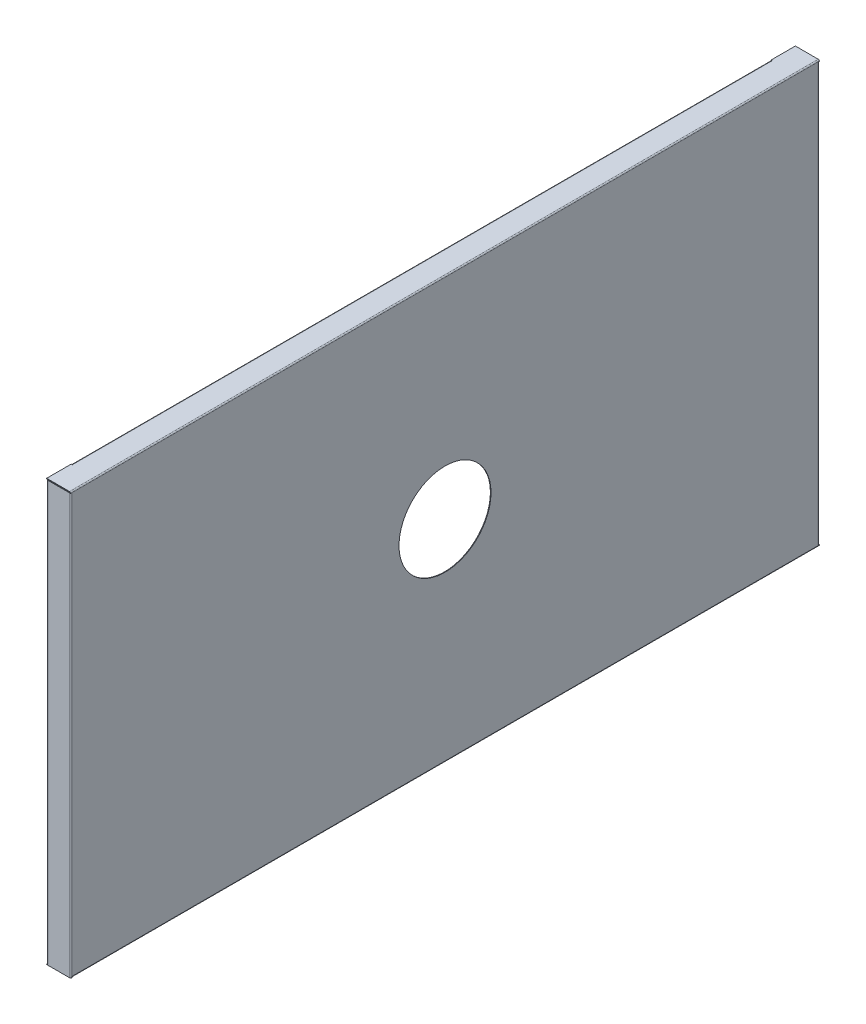
SolidWorks part; units mm, degrees
note: The reader was unsure of these and kept them because the rebuilt part matched: flange length of "Edge-Flange1", "Edge-Flange2", "Edge-Flange3", "Edge-Flange4", "Edge-Flange5", "Edge-Flange6", "Edge-Flange7", "Edge-Flange8".
ref_plane "Front Plane" through (0, 0, 0) normal (0, 0, 1) x (1, 0, 0)
ref_plane "Top Plane" through (0, 0, 0) normal (0, 1, 0) x (1, 0, 0)
ref_plane "Right Plane" through (0, 0, 0) normal (1, 0, 0) x (0, 0, -1)
sketch "Sketch1" plane through (0, 0, 0) normal (1, 0, 0) x (0, 0, -1)
  line L1 (-467.95, -263.2) -> (467.95, -263.2)
  line L2 (-467.95, -263.2) -> (-467.95, 263.2)
  line L3 (-467.95, 263.2) -> (467.95, 263.2)
  line L4 (467.95, -263.2) -> (467.95, 263.2)
  line L5 (-467.95, -263.2) -> (467.95, 263.2) construction
  line L6 (-467.95, 263.2) -> (467.95, -263.2) construction
  circle A0 centre (0, 0) radius 57.5
  point P0 (0, 0)
  dimension "D3" = 115
  dimension "D1" = 935.9
  dimension "D2" = 526.4
base flange "Base-Flange1" sketch "Sketch1" thickness 0.7366 reverse thickness direction no parameters "D1"=0.7366
edge flange "Edge-Flange1" sketch "Sketch8" flange angle 90 flange length 30 flange position material inside bend radius 0.7366 thickness 0.7366 relief rectangular parameters "D6"=10
sketch "Sketch8" plane through (-0.7366, 263.2, 0) normal (0, 1, 0) x (0, 0, -1)
  line L0 (467.95, 0) -> (-467.95, 0) construction
  line L1 (467.95, 0) -> (-467.95, 0)
  line L2 (-467.95, 0) -> (-467.95, 29.2634)
  line L3 (-467.95, 29.2634) -> (467.95, 29.2634)
  line L4 (467.95, 29.2634) -> (467.95, 0)
bend "EdgeBend1" bend radius 0.7366 bend angle 90 parameters "D5"=1
edge flange "Edge-Flange2" sketch "Sketch11" flange angle 90 flange length 30 flange position material inside bend radius 0.7366 thickness 0.7366 relief none parameters "D6"=10
sketch "Sketch11" plane through (-0.7366, 0, 467.95) normal (0, 0, 1) x (0, 1, 0)
  line L0 (261.7268, 0) -> (-263.2, 0) construction
  line L1 (261.7268, 0) -> (-263.2, 0)
  line L2 (-263.2, 0) -> (-263.2, 29.2634)
  line L3 (-263.2, 29.2634) -> (261.7268, 29.2634)
  line L4 (261.7268, 29.2634) -> (261.7268, 0)
bend "EdgeBend2" bend radius 0.7366 bend angle 90 parameters "D5"=2
edge flange "Edge-Flange3" sketch "Sketch14" flange angle 90 flange length 30 flange position material inside bend radius 0.7366 thickness 0.7366 relief none parameters "D6"=10
sketch "Sketch14" plane through (-0.7366, -263.2, 0) normal (0, -1, 0) x (0, 0, 1)
  line L0 (466.4768, 0) -> (-467.95, 0) construction
  line L1 (466.4768, 0) -> (-467.95, 0)
  line L2 (-467.95, 0) -> (-467.95, 29.2634)
  line L3 (-467.95, 29.2634) -> (466.4768, 29.2634)
  line L4 (466.4768, 29.2634) -> (466.4768, 0)
bend "EdgeBend3" bend radius 0.7366 bend angle 90 parameters "D5"=3
edge flange "Edge-Flange4" sketch "Sketch17" flange angle 90 flange length 30 flange position material inside bend radius 0.7366 thickness 0.7366 relief none parameters "D6"=10
sketch "Sketch17" plane through (-0.7366, 0, -467.95) normal (0, 0, -1) x (0, -1, 0)
  line L0 (261.7268, 0) -> (-261.7268, 0) construction
  line L1 (261.7268, 0) -> (-261.7268, 0)
  line L2 (-261.7268, 0) -> (-261.7268, 29.2634)
  line L3 (-261.7268, 29.2634) -> (261.7268, 29.2634)
  line L4 (261.7268, 29.2634) -> (261.7268, 0)
bend "EdgeBend4" bend radius 0.7366 bend angle 90 parameters "D5"=4
edge flange "Edge-Flange5" sketch "Sketch20" flange angle 90 flange length 30 flange position material inside bend radius 0.7366 thickness 0.7366 relief rectangular parameters "D6"=10
sketch "Sketch20" plane through (-30, 262.4634, 0) normal (-1, 0, 0) x (0, 0, -1)
  line L0 (467.95, 0) -> (-467.95, 0) construction
  line L1 (437.0134, 0) -> (-437.0134, 0)
  line L2 (-437.0134, 0) -> (-437.0134, 29.2634)
  line L3 (-437.0134, 29.2634) -> (437.0134, 29.2634)
  line L4 (437.0134, 29.2634) -> (437.0134, 0)
  line L5 (467.2134, 524.1902) -> (467.2134, 0.7366) construction
  line L6 (-467.2134, 0.7366) -> (-467.2134, 525.6634) construction
  dimension "D1" = 30.2
  dimension "D2" = 30.2
bend "EdgeBend5" bend radius 0.7366 bend angle 90 parameters "D5"=5
edge flange "Edge-Flange6" sketch "Sketch23" flange angle 90 flange length 30 flange position material inside bend radius 0.7366 thickness 0.7366 relief rectangular parameters "D6"=10
sketch "Sketch23" plane through (-30, -262.4634, 0) normal (-1, 0, 0) x (0, 0, 1)
  line L0 (466.4768, 0) -> (-467.95, 0) construction
  line L1 (437.0134, 0) -> (-437.0134, 0)
  line L2 (-437.0134, 0) -> (-437.0134, 29.2634)
  line L3 (-437.0134, 29.2634) -> (437.0134, 29.2634)
  line L4 (437.0134, 29.2634) -> (437.0134, 0)
  line L5 (467.2134, 524.1902) -> (467.2134, -0.7366) construction
  line L6 (-467.2134, 0.7366) -> (-467.2134, 524.1902) construction
  dimension "D1" = 30.2
  dimension "D2" = 30.2
bend "EdgeBend6" bend radius 0.7366 bend angle 90 parameters "D5"=6
edge flange "Edge-Flange7" sketch "Sketch26" flange angle 90 flange length 30 flange position material inside bend radius 0.7366 thickness 0.7366 relief rectangular parameters "D6"=10
sketch "Sketch26" plane through (-30, 0, -467.2134) normal (-1, 0, 0) x (0, -1, 0)
  line L0 (261.7268, 0) -> (-261.7268, 0) construction
  line L1 (261.7268, 0) -> (-261.7268, 0)
  line L2 (-261.7268, 0) -> (-261.7268, 29.2634)
  line L3 (-261.7268, 29.2634) -> (261.7268, 29.2634)
  line L4 (261.7268, 29.2634) -> (261.7268, 0)
bend "EdgeBend7" bend radius 0.7366 bend angle 90 parameters "D5"=7
edge flange "Edge-Flange8" sketch "Sketch29" flange angle 90 flange length 30 flange position material inside bend radius 0.7366 thickness 0.7366 relief rectangular parameters "D6"=10
sketch "Sketch29" plane through (-30, 0, 467.2134) normal (1, 0, 0) x (0, -1, 0)
  line L1 (263.2, 0) -> (-261.7268, 0) construction
  line L2 (-261.7268, 0) -> (-261.7268, 29.2634)
  line L3 (-261.7268, 29.2634) -> (262.2634, 29.2634)
  line L4 (262.2634, 29.2634) -> (262.2634, 0)
  line L5 (262.2634, 0) -> (-261.7268, 0)
  line L6 (262.4634, 0.7366) -> (262.4634, 29.8317) construction
  dimension "D1" = 0.2
bend "EdgeBend8" bend radius 0.7366 bend angle 90 parameters "D5"=8
sketch "Bend-Lines1" [suppressed] plane through (0, 0, 0) normal (0, 1, 0) x (1, 0, 0)
sketch "Bounding-Box1" [suppressed] plane through (0, 0, 0) normal (0, 1, 0) x (1, 0, 0)
sheet metal parameters "Sheet-Metal1" thickness 0.7366 parameters "D1"=0.7366
flat pattern "Flat-Pattern1" [suppressed]
sketch "Bend-Lines2" plane through (0, 0, 0) normal (0, 1, 0) x (1, 0, 0)
sketch3d "Bounding-Box2" [suppressed]
  line L0 (-468.45, -263.7, 0) -> (468.45, -263.7, 0) construction
  line L1 (-468.45, 263.7, 0) -> (468.45, 263.7, 0) construction
  line L2 (-468.45, -263.7, 0) -> (-468.45, 263.7, 0) construction
  line L3 (468.45, -263.7, 0) -> (468.45, 263.7, 0) construction
sheet metal parameters "Sheet-Metal2" thickness 0.7366 parameters "D1"=0.7366
flat pattern "Flat-Pattern1"
sketch "Bend-Lines2" plane through (0, 0, 0) normal (1, 0, 0) x (0, 0, -1)
  line L0 (468.45, 263.0946) -> (-468.45, 263.0946) construction
  line L1 (468.45, 263.0946) -> (-468.45, 263.0946) construction
sketch3d "Bounding-Box2" [suppressed]
  line L0 (468.45, -263.7, 0) -> (-468.45, -263.7, 0) construction
  line L1 (468.45, 292.4892, 0) -> (-468.45, 292.4892, 0) construction
  line L2 (468.45, -263.7, 0) -> (468.45, 292.4892, 0) construction
  line L3 (-468.45, -263.7, 0) -> (-468.45, 292.4892, 0) construction
bend of the flat pattern "Flatten-<EdgeBend1>1"
sheet metal parameters "Sheet-Metal3" thickness 0.7366 parameters "D1"=0.7366
flat pattern "Flat-Pattern1"
sketch "Bend-Lines2" plane through (0, 0, 0) normal (1, 0, 0) x (0, 0, -1)
  line L0 (468.45, 263.0946) -> (-468.45, 263.0946) construction
  line L1 (468.45, 263.0946) -> (-468.45, 263.0946) construction
  line L2 (-467.8446, 262.2268) -> (-467.8446, -263.7) construction
  line L3 (-467.8446, 262.2268) -> (-467.8446, -263.7) construction
sketch3d "Bounding-Box2" [suppressed]
  line L0 (468.45, -263.7, 0) -> (-497.2392, -263.7, 0) construction
  line L1 (468.45, 292.4892, 0) -> (-497.2392, 292.4892, 0) construction
  line L2 (468.45, -263.7, 0) -> (468.45, 292.4892, 0) construction
  line L3 (-497.2392, -263.7, 0) -> (-497.2392, 292.4892, 0) construction
bend of the flat pattern "Flatten-<EdgeBend1>1"
bend of the flat pattern "Flatten-<EdgeBend2>1"
sheet metal parameters "Sheet-Metal4" thickness 0.7366 parameters "D1"=0.7366
flat pattern "Flat-Pattern1"
sketch "Bend-Lines2" plane through (0, 0, 0) normal (1, 0, 0) x (0, 0, -1)
  line L0 (468.45, 263.0946) -> (-468.45, 263.0946) construction
  line L1 (468.45, 263.0946) -> (-468.45, 263.0946) construction
  line L2 (-467.8446, 262.2268) -> (-467.8446, -263.7) construction
  line L3 (-467.8446, 262.2268) -> (-467.8446, -263.7) construction
  line L4 (-466.9768, -263.0946) -> (468.45, -263.0946) construction
  line L5 (-466.9768, -263.0946) -> (468.45, -263.0946) construction
sketch3d "Bounding-Box2" [suppressed]
  line L0 (468.45, -292.4892, 0) -> (-497.2392, -292.4892, 0) construction
  line L1 (468.45, 292.4892, 0) -> (-497.2392, 292.4892, 0) construction
  line L2 (468.45, -292.4892, 0) -> (468.45, 292.4892, 0) construction
  line L3 (-497.2392, -292.4892, 0) -> (-497.2392, 292.4892, 0) construction
bend of the flat pattern "Flatten-<EdgeBend1>1"
bend of the flat pattern "Flatten-<EdgeBend2>1"
bend of the flat pattern "Flatten-<EdgeBend3>1"
sheet metal parameters "Sheet-Metal5" thickness 0.7366 parameters "D1"=0.7366
flat pattern "Flat-Pattern1"
sketch "Bend-Lines2" plane through (0, 0, 0) normal (1, 0, 0) x (0, 0, -1)
  line L0 (468.45, 263.0946) -> (-468.45, 263.0946) construction
  line L1 (468.45, 263.0946) -> (-468.45, 263.0946) construction
  line L2 (-467.8446, 262.2268) -> (-467.8446, -263.7) construction
  line L3 (-467.8446, 262.2268) -> (-467.8446, -263.7) construction
  line L4 (-466.9768, -263.0946) -> (468.45, -263.0946) construction
  line L5 (-466.9768, -263.0946) -> (468.45, -263.0946) construction
  line L6 (467.8446, -262.2268) -> (467.8446, 262.2268) construction
  line L7 (467.8446, -262.2268) -> (467.8446, 262.2268) construction
sketch3d "Bounding-Box2" [suppressed]
  line L0 (497.2392, -292.4892, 0) -> (-497.2392, -292.4892, 0) construction
  line L1 (497.2392, 292.4892, 0) -> (-497.2392, 292.4892, 0) construction
  line L2 (497.2392, -292.4892, 0) -> (497.2392, 292.4892, 0) construction
  line L3 (-497.2392, -292.4892, 0) -> (-497.2392, 292.4892, 0) construction
bend of the flat pattern "Flatten-<EdgeBend1>1"
bend of the flat pattern "Flatten-<EdgeBend2>1"
bend of the flat pattern "Flatten-<EdgeBend3>1"
bend of the flat pattern "Flatten-<EdgeBend4>1"
sheet metal parameters "Sheet-Metal6" thickness 0.7366 parameters "D1"=0.7366
flat pattern "Flat-Pattern1"
sketch "Bend-Lines2" plane through (0, 0, 0) normal (1, 0, 0) x (0, 0, -1)
  line L0 (468.45, 263.0946) -> (-468.45, 263.0946) construction
  line L1 (468.45, 263.0946) -> (-468.45, 263.0946) construction
  line L2 (-467.8446, 262.2268) -> (-467.8446, -263.7) construction
  line L3 (-467.8446, 262.2268) -> (-467.8446, -263.7) construction
  line L4 (-466.9768, -263.0946) -> (468.45, -263.0946) construction
  line L5 (-466.9768, -263.0946) -> (468.45, -263.0946) construction
  line L6 (467.8446, -262.2268) -> (467.8446, 262.2268) construction
  line L7 (467.8446, -262.2268) -> (467.8446, 262.2268) construction
  line L8 (437.5134, 291.8838) -> (-437.5134, 291.8838) construction
  line L9 (437.5134, 291.8838) -> (-437.5134, 291.8838) construction
sketch3d "Bounding-Box2" [suppressed]
  line L0 (497.2392, -292.4892, 0) -> (-497.2392, -292.4892, 0) construction
  line L1 (497.2392, 321.2783, 0) -> (-497.2392, 321.2783, 0) construction
  line L2 (497.2392, -292.4892, 0) -> (497.2392, 321.2783, 0) construction
  line L3 (-497.2392, -292.4892, 0) -> (-497.2392, 321.2783, 0) construction
bend of the flat pattern "Flatten-<EdgeBend1>1"
bend of the flat pattern "Flatten-<EdgeBend2>1"
bend of the flat pattern "Flatten-<EdgeBend3>1"
bend of the flat pattern "Flatten-<EdgeBend4>1"
bend of the flat pattern "Flatten-<EdgeBend5>1"
sheet metal parameters "Sheet-Metal7" thickness 0.7366 parameters "D1"=0.7366
flat pattern "Flat-Pattern1"
sketch "Bend-Lines2" plane through (0, 0, 0) normal (1, 0, 0) x (0, 0, -1)
  line L0 (468.45, 263.0946) -> (-468.45, 263.0946) construction
  line L1 (468.45, 263.0946) -> (-468.45, 263.0946) construction
  line L2 (-467.8446, 262.2268) -> (-467.8446, -263.7) construction
  line L3 (-467.8446, 262.2268) -> (-467.8446, -263.7) construction
  line L4 (-466.9768, -263.0946) -> (468.45, -263.0946) construction
  line L5 (-466.9768, -263.0946) -> (468.45, -263.0946) construction
  line L6 (467.8446, -262.2268) -> (467.8446, 262.2268) construction
  line L7 (467.8446, -262.2268) -> (467.8446, 262.2268) construction
  line L8 (437.5134, 291.8838) -> (-437.5134, 291.8838) construction
  line L9 (437.5134, 291.8838) -> (-437.5134, 291.8838) construction
  line L10 (-437.5134, -291.8838) -> (437.5134, -291.8838) construction
  line L11 (-437.5134, -291.8838) -> (437.5134, -291.8838) construction
sketch3d "Bounding-Box2" [suppressed]
  line L0 (497.2392, -321.2783, 0) -> (-497.2392, -321.2783, 0) construction
  line L1 (497.2392, 321.2783, 0) -> (-497.2392, 321.2783, 0) construction
  line L2 (497.2392, -321.2783, 0) -> (497.2392, 321.2783, 0) construction
  line L3 (-497.2392, -321.2783, 0) -> (-497.2392, 321.2783, 0) construction
bend of the flat pattern "Flatten-<EdgeBend1>1"
bend of the flat pattern "Flatten-<EdgeBend2>1"
bend of the flat pattern "Flatten-<EdgeBend3>1"
bend of the flat pattern "Flatten-<EdgeBend4>1"
bend of the flat pattern "Flatten-<EdgeBend5>1"
bend of the flat pattern "Flatten-<EdgeBend6>1"
sheet metal parameters "Sheet-Metal8" thickness 0.7366 parameters "D1"=0.7366
flat pattern "Flat-Pattern1"
sketch "Bend-Lines2" plane through (0, 0, 0) normal (1, 0, 0) x (0, 0, -1)
  line L0 (468.45, 263.0946) -> (-468.45, 263.0946) construction
  line L1 (468.45, 263.0946) -> (-468.45, 263.0946) construction
  line L2 (-467.8446, 262.2268) -> (-467.8446, -263.7) construction
  line L3 (-467.8446, 262.2268) -> (-467.8446, -263.7) construction
  line L4 (-466.9768, -263.0946) -> (468.45, -263.0946) construction
  line L5 (-466.9768, -263.0946) -> (468.45, -263.0946) construction
  line L6 (467.8446, -262.2268) -> (467.8446, 262.2268) construction
  line L7 (467.8446, -262.2268) -> (467.8446, 262.2268) construction
  line L8 (437.5134, 291.8838) -> (-437.5134, 291.8838) construction
  line L9 (437.5134, 291.8838) -> (-437.5134, 291.8838) construction
  line L10 (-437.5134, -291.8838) -> (437.5134, -291.8838) construction
  line L11 (-437.5134, -291.8838) -> (437.5134, -291.8838) construction
  line L12 (496.6338, -262.2268) -> (496.6338, 262.2268) construction
  line L13 (496.6338, -262.2268) -> (496.6338, 262.2268) construction
sketch3d "Bounding-Box2" [suppressed]
  line L0 (526.0283, -321.2783, 0) -> (-497.2392, -321.2783, 0) construction
  line L1 (526.0283, 321.2783, 0) -> (-497.2392, 321.2783, 0) construction
  line L2 (526.0283, -321.2783, 0) -> (526.0283, 321.2783, 0) construction
  line L3 (-497.2392, -321.2783, 0) -> (-497.2392, 321.2783, 0) construction
bend of the flat pattern "Flatten-<EdgeBend1>1"
bend of the flat pattern "Flatten-<EdgeBend2>1"
bend of the flat pattern "Flatten-<EdgeBend3>1"
bend of the flat pattern "Flatten-<EdgeBend4>1"
bend of the flat pattern "Flatten-<EdgeBend5>1"
bend of the flat pattern "Flatten-<EdgeBend6>1"
bend of the flat pattern "Flatten-<EdgeBend7>1"
sheet metal parameters "Sheet-Metal9" thickness 0.7366 parameters "D1"=0.7366
flat pattern "Flat-Pattern1"
sketch "Bend-Lines2" plane through (0, 0, 0) normal (1, 0, 0) x (0, 0, -1)
  line L0 (467.95, 262.5946) -> (-467.95, 262.5946) construction
  line L1 (467.95, 262.5946) -> (-467.95, 262.5946) construction
  line L2 (-467.3446, 261.7268) -> (-467.3446, -263.2) construction
  line L3 (-467.3446, 261.7268) -> (-467.3446, -263.2) construction
  line L4 (-466.4768, -262.5946) -> (467.95, -262.5946) construction
  line L5 (-466.4768, -262.5946) -> (467.95, -262.5946) construction
  line L6 (467.3446, -261.7268) -> (467.3446, 261.7268) construction
  line L7 (467.3446, -261.7268) -> (467.3446, 261.7268) construction
  line L8 (437.0134, 291.3838) -> (-437.0134, 291.3838) construction
  line L9 (437.0134, 291.3838) -> (-437.0134, 291.3838) construction
  line L10 (-437.0134, -291.3838) -> (437.0134, -291.3838) construction
  line L11 (-437.0134, -291.3838) -> (437.0134, -291.3838) construction
  line L12 (496.1338, -261.7268) -> (496.1338, 261.7268) construction
  line L13 (496.1338, -261.7268) -> (496.1338, 261.7268) construction
  line L14 (-496.1338, 261.7268) -> (-496.1338, -262.2634) construction
  line L15 (-496.1338, 261.7268) -> (-496.1338, -262.2634) construction
sketch3d "Bounding-Box2" [suppressed]
  line L0 (525.5283, -320.7783, 0) -> (-525.5283, -320.7783, 0) construction
  line L1 (525.5283, 320.7783, 0) -> (-525.5283, 320.7783, 0) construction
  line L2 (525.5283, -320.7783, 0) -> (525.5283, 320.7783, 0) construction
  line L3 (-525.5283, -320.7783, 0) -> (-525.5283, 320.7783, 0) construction
bend of the flat pattern "Flatten-<EdgeBend1>1"
bend of the flat pattern "Flatten-<EdgeBend2>1"
bend of the flat pattern "Flatten-<EdgeBend3>1"
bend of the flat pattern "Flatten-<EdgeBend4>1"
bend of the flat pattern "Flatten-<EdgeBend5>1"
bend of the flat pattern "Flatten-<EdgeBend6>1"
bend of the flat pattern "Flatten-<EdgeBend7>1"
bend of the flat pattern "Flatten-<EdgeBend8>1"
